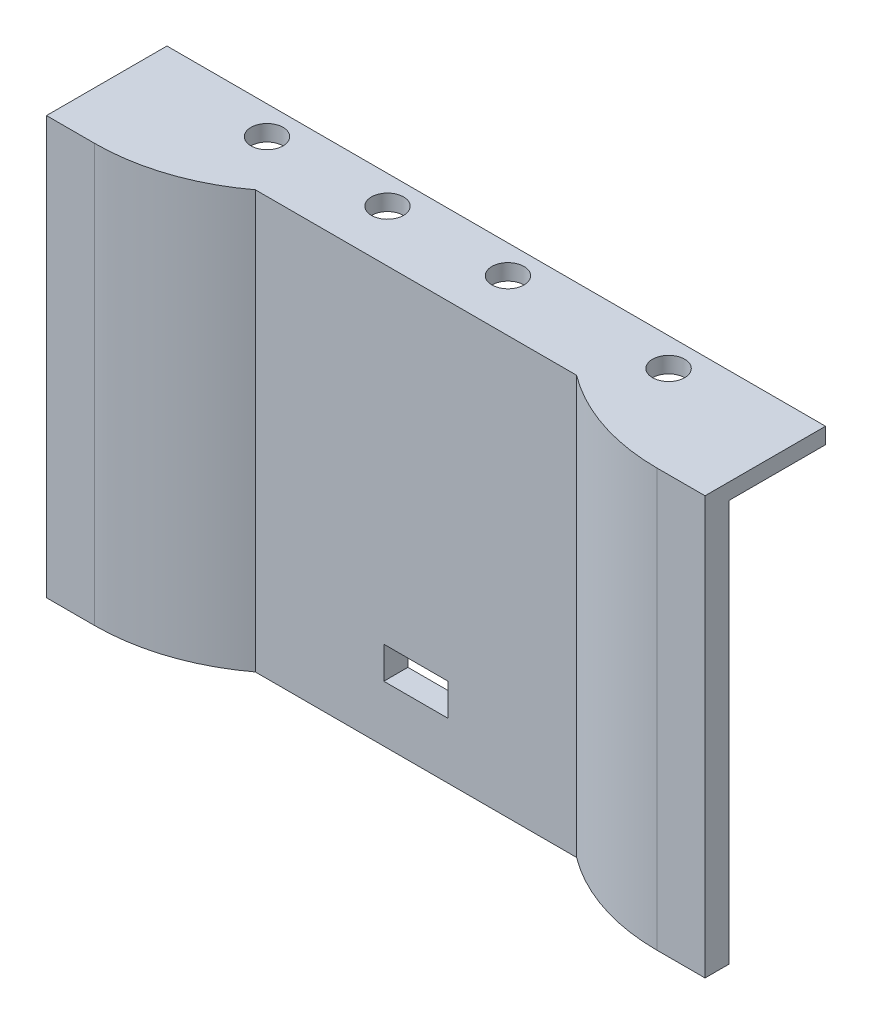
SolidWorks part; units mm, degrees
ref_plane "Front Plane" through (0, 0, 0) normal (0, 0, 1) x (1, 0, 0)
ref_plane "Top Plane" through (0, 0, 0) normal (0, 1, 0) x (1, 0, 0)
ref_plane "Right Plane" through (0, 0, 0) normal (1, 0, 0) x (0, 0, -1)
sketch "Sketch1" plane through (0, 0, 0) normal (0, 1, 0) x (1, 0, 0)
  line L0 (0, 0) -> (0, -5) construction
  line L1 (-41, -7.5) -> (-30, -7.5)
  line L2 (-41, -7.5) -> (-41, 7.5)
  line L3 (-41, 7.5) -> (41, 7.5)
  line L4 (41, -7.5) -> (41, 7.5)
  line L5 (-41, -7.5) -> (41, 7.5) construction
  line L6 (-41, 7.5) -> (41, -7.5) construction
  line L7 (30, -7.5) -> (41, -7.5)
  line L8 (-30, -2.5) -> (30, -2.5)
  line L9 (-30, -2.5) -> (-30, -7.5)
  line L11 (30, -2.5) -> (30, -7.5)
  line L12 (-30, -2.5) -> (30, -7.5) construction
  line L13 (0, -5) -> (30, -2.5) construction
  point P0 (0, 0)
  point P8 (0, -5)
  dimension "D1" = 82
  dimension "D2" = 15
  dimension "D3" = 60
  dimension "D4" = 10
extrude "Boss-Extrude1" add sketch "Sketch1" along normal blind 52
sketch "Sketch2" plane through (0, 52, 0) normal (0, 1, 0) x (1, 0, 0)
  line L0 (-41, 7.5) -> (-41, -7.5) construction
  line L1 (-41, -4.5) -> (-33, -4.5)
  line L2 (-41, -4.5) -> (-41, 7.5)
  line L3 (-41, 7.5) -> (-33, 7.5)
  line L4 (-33, -4.5) -> (-33, 0.5)
  line L5 (41, 7.5) -> (-41, 7.5) construction
  line L6 (-41, -7.5) -> (-30, -7.5) construction
  line L7 (-30, -7.5) -> (-30, -2.5) construction
  line L8 (41, -7.5) -> (41, 7.5) construction
  line L9 (41, -4.5) -> (33, -4.5)
  line L10 (41, -4.5) -> (41, 7.5)
  line L11 (41, 7.5) -> (33, 7.5)
  line L12 (33, -4.5) -> (33, 0.5)
  line L13 (30, -7.5) -> (41, -7.5) construction
  line L14 (30, -2.5) -> (30, -7.5) construction
  line L15 (-30, -2.5) -> (30, -2.5) construction
  line L16 (-33, 7.5) -> (33, 7.5)
  line L18 (-33, 0.5) -> (33, 0.5)
  dimension "D1" = 3
  dimension "D2" = 3
  dimension "D3" = 3
  dimension "D4" = 3
  dimension "D5" = 3
extrude "Cut-Extrude1" cut sketch "Sketch2" against normal blind 52
chamfer "Chamfer2" distance 10 angle 45 2 edges at (30, 26, 2.5) (-30, 26, 2.5)
sketch "Sketch3" plane through (0, 0, 2.5) normal (0, 0, 1) x (1, 0, 0)
  line L0 (0, 0) -> (0, 52) construction
  line L1 (-20, 52) -> (20, 52) construction
  line L3 (-4, 7) -> (4, 7)
  line L4 (-4, 7) -> (-4, 11)
  line L5 (-4, 11) -> (4, 11)
  line L6 (4, 7) -> (4, 11)
  line L7 (-4, 7) -> (4, 11) construction
  line L8 (-4, 11) -> (4, 7) construction
  point P5 (0, 9)
  dimension "D1" = 41
  dimension "D2" = 4
  dimension "D3" = 8
extrude "Cut-Extrude2" cut sketch "Sketch3" against normal blind 52
fillet "Fillet1" radius 25 2 edges at (25, 26, 7.5) (-25, 26, 7.5)
sketch "Sketch4" plane through (0, 52, 0) normal (0, 1, 0) x (1, 0, 0)
  line L0 (-41, -4.5) -> (-33, -4.5) construction
  line L1 (-33, 0.5) -> (-30, 0.5)
  line L2 (-33, 0.5) -> (-33, -4.5)
  line L3 (-33, -4.5) -> (-30, -4.5)
  line L4 (-30, 0.5) -> (-30, -4.5)
  line L6 (33, 0.5) -> (30, 0.5)
  line L7 (33, 0.5) -> (33, -4.5)
  line L8 (33, -4.5) -> (30, -4.5)
  line L9 (30, 0.5) -> (30, -4.5)
  dimension "D1" = 3
  dimension "D2" = 3
extrude "Cut-Extrude3" cut sketch "Sketch4" against normal blind 52
sketch "Sketch5" plane through (0, 52, 0) normal (0, 1, 0) x (1, 0, 0)
  line L0 (-41, -4.5) -> (-30, -4.5) construction
  line L1 (-30, 0.5) -> (30, 0.5)
  line L3 (-30, 7.5) -> (30, 7.5)
  line L6 (-41, -4.5) -> (-30, -4.5)
  line L7 (-41, -4.5) -> (-41, 7.5)
  line L8 (-41, 7.5) -> (-30, 7.5)
  line L9 (-30, -4.5) -> (-30, 0.5)
  line L10 (41, -4.5) -> (30, -4.5)
  line L11 (41, -4.5) -> (41, 7.5)
  line L12 (41, 7.5) -> (30, 7.5)
  line L13 (30, -4.5) -> (30, 0.5)
  dimension "D1" = 12
extrude "Boss-Extrude2" add sketch "Sketch5" against normal blind 2
sketch "Sketch6" plane through (0, 52, 0) normal (0, 1, 0) x (1, 0, 0)
  line L0 (-41, 7.5) -> (-41, -7.5) construction
  line L1 (-25, 3.96) -> (33.6457, 3.96) construction
  line L2 (41, 7.5) -> (-41, 7.5) construction
  circle A0 centre (-25, 3.96) radius 2
  circle A1 centre (-10, 3.96) radius 2
  circle A2 centre (5, 3.96) radius 2
  circle A3 centre (25, 3.96) radius 2
  dimension "D1" = 16
  dimension "D2" = 15
  dimension "D4" = 4
  dimension "D5" = 20
  dimension "D3" = 15
  dimension "D6" = 3.54
extrude "Cut-Extrude4" cut sketch "Sketch6" against normal blind 21
